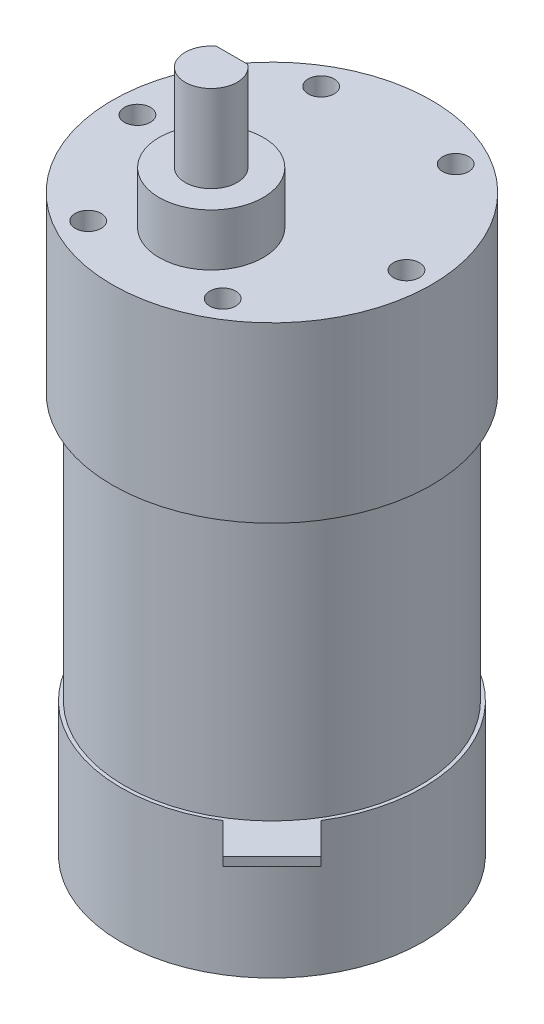
SolidWorks part; units mm, degrees
material "7075-T6 (SN)"
ref_plane "Front Plane" through (0, 0, 0) normal (0, 0, 1) x (1, 0, 0)
ref_plane "Top Plane" through (0, 0, 0) normal (0, 1, 0) x (1, 0, 0)
ref_plane "Right Plane" through (0, 0, 0) normal (1, 0, 0) x (0, 0, -1)
ref_plane "Plane1" through (0, 0, 4.6) normal (0, 0, 1) x (1, 0, 0)
ref_axis "Axis2" through (0, 0, 0) along (0, 0, 1)
sketch "Sketch1" plane through (0, 0, 0) normal (0, 1, 0) x (1, 0, 0)
  circle A0 centre (0, 0) radius 17.4
  dimension "D1" = 34.8
extrude "Boss-Extrude1" add sketch "Sketch1" along normal blind 15.4
sketch "Sketch6" plane through (0, 15.4, 0) normal (0, 1, 0) x (1, 0, 0)
  circle A0 centre (0, 0) radius 17
  dimension "D1" = 34
extrude "Boss-Extrude5" add sketch "Sketch6" along normal blind 30.7
sketch "Sketch7" plane through (0, 46.1, 0) normal (0, 1, 0) x (1, 0, 0)
  circle A0 centre (0, 0) radius 18.4
  dimension "D1" = 36.8
extrude "Boss-Extrude6" add sketch "Sketch7" along normal blind 20
sketch "Sketch2" plane through (0, 66.1, 0) normal (0, 1, 0) x (1, 0, 0)
  line L0 (0, 17.4) -> (0, -17.4) construction
  circle A0 centre (0, 0) radius 17.4 construction
  circle A1 centre (0, -7) radius 6
  point P7 (0, 0)
  dimension "D2" = 12
  dimension "D1" = 7
extrude "Boss-Extrude2" add sketch "Sketch2" along normal blind 6
sketch "Sketch3" plane through (0, 72.1, 0) normal (0, 1, 0) x (1, 0, 0)
  circle A0 centre (0, -7) radius 3
  dimension "D1" = 6
extrude "Boss-Extrude4" add sketch "Sketch3" along normal blind 10
sketch "Sketch4" plane through (0, 0, 4.6) normal (0, 0, 1) x (1, 0, 0)
  line L0 (-3, 82.1) -> (3, 82.1)
  line L1 (-3, 82.1) -> (-3, 74.1)
  line L2 (3, 82.1) -> (3, 74.1)
  line L3 (-3, 74.1) -> (3, 74.1)
  line L4 (6, 72.1) -> (-6, 72.1) construction
  dimension "D1" = 2
extrude "Cut-Extrude1" cut sketch "Sketch4" against normal blind 10
sketch "Sketch8" plane through (0, 15.4, 0) normal (0, -1, 0) x (1, 0, 0)
  line L0 (2.8284, -2.8284) -> (-2.8284, 2.8284)
  line L1 (2.8284, -2.8284) -> (18.3848, 12.7279)
  line L2 (-2.8284, 2.8284) -> (12.7279, 18.3848)
  line L3 (18.3848, 12.7279) -> (12.7279, 18.3848)
  line L4 (17.4, 0) -> (-17.4, 0) construction
  circle A0 centre (0, 0) radius 17.4 construction
  point P0 (0, 0)
  point P12 (0, 0)
  dimension "D1" = 8
  dimension "D2" = 45
  dimension "D3" = 22
extrude "Boss-Extrude7" add sketch "Sketch8" along normal blind 1
sketch "Sketch5" plane through (0, 66.1, 0) normal (0, 1, 0) x (1, 0, 0)
  line L0 (0, 17.4) -> (0, -17.4) construction
  line L1 (-7.75, 13.4234) -> (7.75, 13.4234) construction
  line L2 (-15.5, 0) -> (15.5, 0) construction
  line L3 (-15.5, 0) -> (7.75, -13.4234) construction
  line L4 (-7.75, 13.4234) -> (15.5, 0) construction
  line L5 (-7.75, -13.4234) -> (7.75, -13.4234) construction
  circle A0 centre (0, 0) radius 17.4 construction
  circle A1 centre (-7.75, 13.4234) radius 1.5
  circle A2 centre (7.75, 13.4234) radius 1.5
  circle A3 centre (-15.5, 0) radius 1.5
  circle A4 centre (15.5, 0) radius 1.5
  circle A5 centre (7.75, -13.4234) radius 1.5
  circle A6 centre (-7.75, -13.4234) radius 1.5
  point P8 (0, 13.4234)
  point P23 (0, -13.4234)
  point P26 (0, 0)
  dimension "D1" = 3
  dimension "D2" = 15.5
  dimension "D3" = 15.5
  dimension "D4" = 31
extrude "Cut-Extrude2" cut sketch "Sketch5" against normal blind 3
ref_axis "Shaft Axis" through (0, 82.1, 7) along (0, -1, 0)
